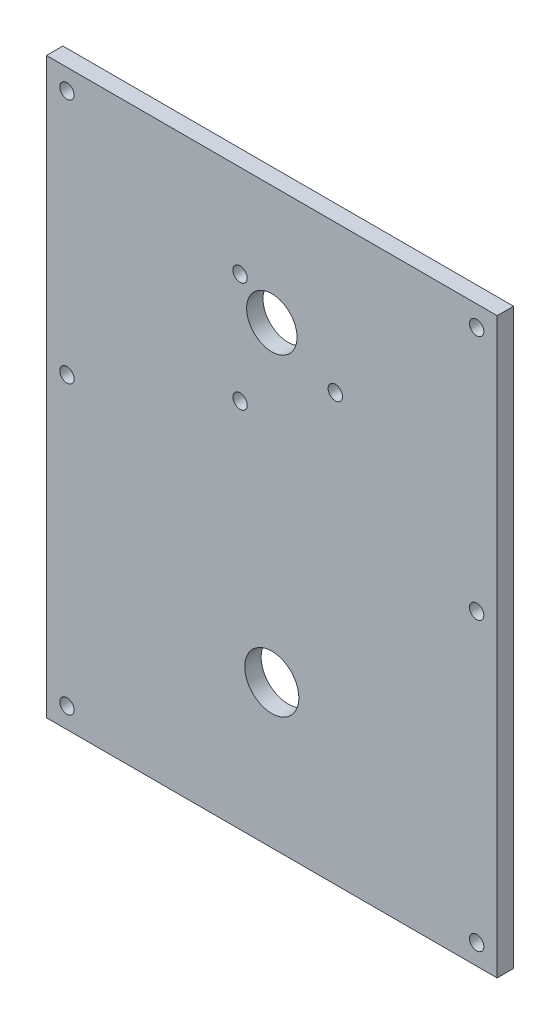
SolidWorks part; units mm, degrees
ref_plane "正面" through (0, 0, 0) normal (0, 0, 1) x (1, 0, 0)
ref_plane "平面" through (0, 0, 0) normal (0, 1, 0) x (1, 0, 0)
ref_plane "右側面" through (0, 0, 0) normal (1, 0, 0) x (0, 0, -1)
sketch "ｽｹｯﾁ1" plane through (0, 0, 0) normal (0, 0, 1) x (1, 0, 0)
  line L0 (55, 0) -> (55, 35)
  line L1 (0, 0) -> (110, 0)
  line L2 (0, 0) -> (0, 140)
  line L3 (0, 140) -> (110, 140)
  line L4 (110, 0) -> (110, 140)
  line L5 (0, 140) -> (5, 140)
  line L6 (0, 140) -> (0, 135)
  line L7 (0, 135) -> (5, 135)
  line L8 (5, 140) -> (5, 135)
  line L9 (110, 0) -> (105, 0)
  line L10 (110, 0) -> (110, 5)
  line L11 (110, 5) -> (105, 5)
  line L12 (105, 0) -> (105, 5)
  line L13 (55, 35) -> (55, 104)
  line L14 (55, 104) -> (70.5, 104)
  line L15 (55, 104) -> (47.25, 117.4234)
  line L16 (55, 104) -> (47.25, 90.5766)
  circle A0 centre (5, 135) radius 1.75
  circle A1 centre (5, 5) radius 1.75
  circle A2 centre (105, 135) radius 1.75
  circle A3 centre (105, 5) radius 1.75
  circle A4 centre (55, 35) radius 6.6
  circle A6 centre (70.5, 104) radius 1.75
  circle A7 centre (47.25, 117.4234) radius 1.75
  circle A8 centre (47.25, 90.5766) radius 1.75
  circle A9 centre (105, 75) radius 1.75
  circle A10 centre (5, 75) radius 1.75
  circle A11 centre (55, 111) radius 6.15
  point P8 (5, 137.5)
  dimension "D7" = 35
  dimension "D8" = 13.2
  dimension "D13" = 7
  dimension "D15" = 55
  dimension "D14" = 135
  dimension "D1" = 110
  dimension "D2" = 140
  dimension "D3" = 5
  dimension "D4" = 5
  dimension "D5" = 5
  dimension "D6" = 5
  dimension "D9" = 69
  dimension "D10" = 15.5
  dimension "D11" = 120
  dimension "D12" = 120
  dimension "D16" = 5
  dimension "D17" = 70
  dimension "D18" = 70
  dimension "D19" = 5
extrude "ﾎﾞｽ - 押し出し1" add sketch "ｽｹｯﾁ1" along normal blind 4 contours A8 A7 A6 A11 A4 L1 L12 A3 L11 L4 L3 L8 A0 L7 L2 A2 A1 | A0 L8 L3 L2 L7 | A3 L12 L1 L4 L11 region at (27.5, 1.7804, 0) region at (107.6871, 2.3129, 0) region at (2.3129, 137.6871, 0)
